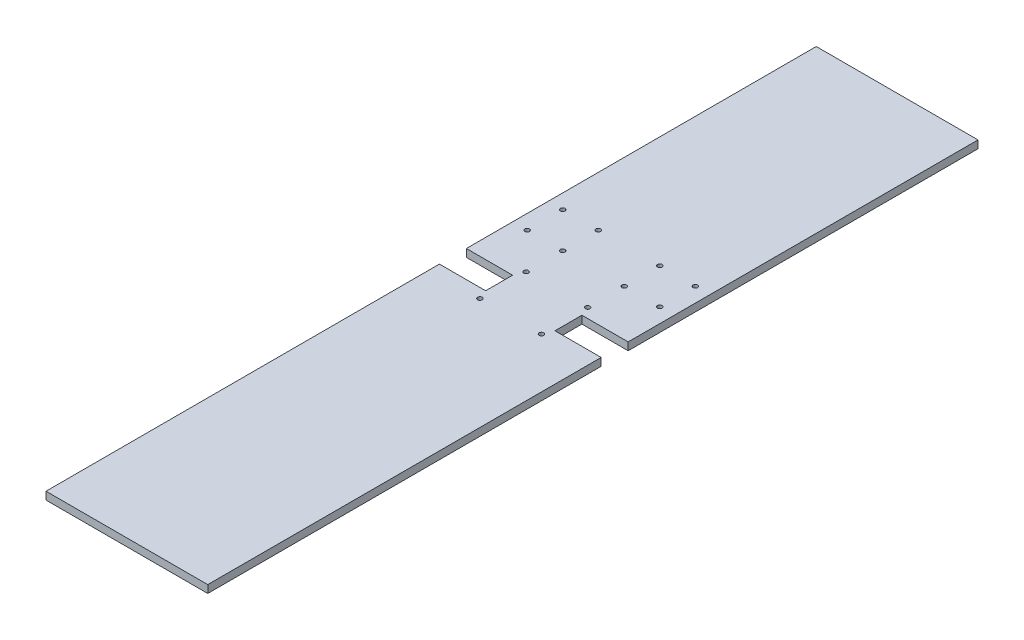
SolidWorks part; units mm, degrees
ref_plane "Front Plane" through (0, 0, 0) normal (0, 0, 1) x (1, 0, 0)
ref_plane "Top Plane" through (0, 0, 0) normal (0, 1, 0) x (1, 0, 0)
ref_plane "Right Plane" through (0, 0, 0) normal (1, 0, 0) x (0, 0, -1)
sketch "Sketch1" plane through (0, 0, 0) normal (0, 1, 0) x (1, 0, 0)
  line L0 (-52.5, 235.8631) -> (-52.5, 8.75)
  line L1 (-20, -15) -> (20, -15) construction
  line L2 (-20, -15) -> (-20, 15) construction
  line L3 (-20, 15) -> (20, 15) construction
  line L4 (20, -15) -> (20, 15) construction
  line L5 (-20, -15) -> (20, 15) construction
  line L6 (-20, 15) -> (20, -15) construction
  line L7 (-52.5, 8.75) -> (-22.5, 8.75)
  line L8 (-22.5, 8.75) -> (-22.5, -8.75)
  line L9 (-22.5, -8.75) -> (-52.5, -8.75)
  line L10 (-52.5, -8.75) -> (-52.5, -264.1369)
  line L12 (-55, 0) -> (55, 0) construction
  line L13 (0, -55) -> (0, 55) construction
  line L14 (52.5, -8.75) -> (52.5, -264.1369)
  line L15 (22.5, -8.75) -> (52.5, -8.75)
  line L16 (22.5, 8.75) -> (22.5, -8.75)
  line L17 (52.5, 8.75) -> (22.5, 8.75)
  line L18 (52.5, 235.8631) -> (52.5, 8.75)
  line L19 (-52.5, 235.8631) -> (52.5, 235.8631)
  line L20 (52.5, -264.1369) -> (-52.5, -264.1369)
  circle A0 centre (-20, 15) radius 1.5
  circle A1 centre (20, 15) radius 1.5
  circle A2 centre (20, -15) radius 1.5
  circle A3 centre (-20, -15) radius 1.5
  point P0 (0, 0)
  point P14 (-22.5, 0)
  dimension "D7" = 3
  dimension "D1" = 30
  dimension "D2" = 40
  dimension "D3" = 17.5
  dimension "D4" = 22.5
  dimension "D5" = 500
  dimension "D6" = 30
extrude "Boss-Extrude1" add sketch "Sketch1" along normal blind 5
sketch "Sketch3" plane through (0, 5, 0) normal (0, 1, 0) x (1, 0, 0)
  line L0 (-52.5, 8.75) -> (-22.5, 8.75) construction
  line L1 (-43.08, 61.83) -> (-20, 61.83) construction
  line L2 (-43.08, 61.83) -> (-43.08, 38.75) construction
  line L3 (-43.08, 38.75) -> (-20, 38.75) construction
  line L4 (-20, 61.83) -> (-20, 38.75) construction
  line L5 (-43.08, 61.83) -> (-20, 38.75) construction
  line L6 (-43.08, 38.75) -> (-20, 61.83) construction
  line L7 (0, -2.75) -> (0, 2.75) construction
  line L8 (43.08, 61.83) -> (20, 38.75) construction
  line L9 (43.08, 38.75) -> (20, 61.83) construction
  line L10 (43.08, 61.83) -> (20, 61.83) construction
  line L11 (20, 61.83) -> (20, 38.75) construction
  line L12 (43.08, 61.83) -> (43.08, 38.75) construction
  line L13 (43.08, 38.75) -> (20, 38.75) construction
  point P6 (-43.08, 61.83)
  point P7 (-20, 61.83)
  point P8 (-43.08, 38.75)
  point P17 (20, 61.83)
  point P18 (43.08, 61.83)
  point P19 (20, 38.75)
  point P20 (43.08, 38.75)
  point P21 (20, 50.29)
  point P22 (-20, 38.75)
  point P32 (0, 0)
  point P33 (0, 0)
  point P34 (0, 0)
  point P35 (0, 0)
  dimension "D1" = 23.08
  dimension "D2" = 23.08
  dimension "D4" = 30
  dimension "D5" = 40
hole_wizard "Ø3.0mm Dowel Hole1" positions "Sketch3" profile "Sketch4" hole size "Ø3.0" standard "ANSI Metric" end condition through all
sketch "Sketch4" plane through (-20, 5, -38.75) normal (1, 0, 0) x (0, 0, 1)
  line L0 (0, 0) -> (0, 5)
  line L1 (0, 5) -> (1.5, 5)
  line L2 (1.5, 5) -> (1.5, 0)
  line L5 (1.5, 0) -> (0, 0)
  line L11 (0, -6.35) -> (0, 107.95) construction
  dimension "Thru Hole Dia." = 3
  dimension "Thru Hole Depth" = 5
